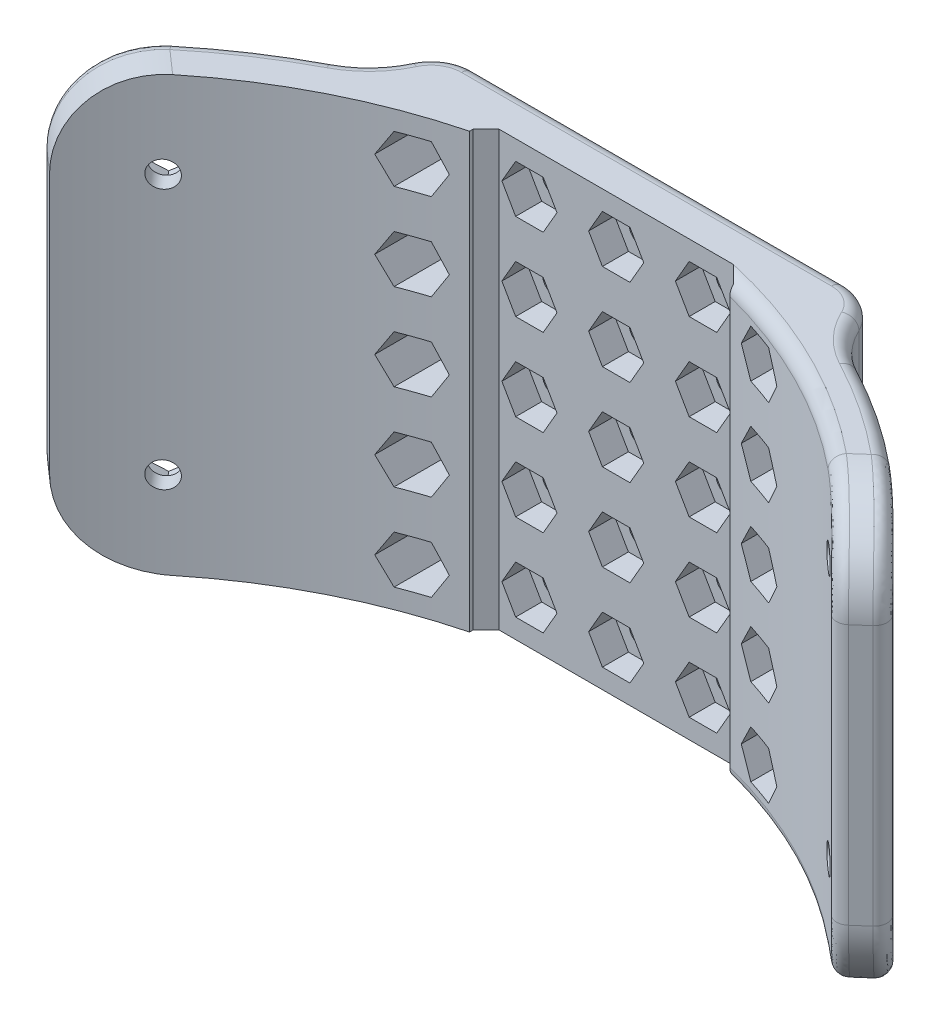
SolidWorks part; units mm, degrees
ref_plane "Front Plane" through (0, 0, 0) normal (0, 0, 1) x (1, 0, 0)
ref_plane "Top Plane" through (0, 0, 0) normal (0, 1, 0) x (1, 0, 0)
ref_plane "Right Plane" through (0, 0, 0) normal (1, 0, 0) x (0, 0, -1)
sketch "草图1" plane through (0, 0, 0) normal (0, 1, 0) x (1, 0, 0)
  line L1 (0, -1000) -> (0, 49000) construction
  line L2 (-15, 58.0948) -> (0, 0) construction
  line L3 (0, 0) -> (-45, 39.6863) construction
  line L6 (-48.75, 42.9935) -> (-45, 39.6863)
  line L7 (-15, 58.0948) -> (-15, 60)
  line L8 (-15, 60) -> (0, 60)
  line L9 (0, 60) -> (0, 65)
  line L11 (0, 65) -> (-25, 65)
  line L13 (-25, 65) -> (-25, 60)
  arc A0 (-45, 39.6863) -> (-15, 58.0948) centre (0, 0) cw
  arc A1 (-48.75, 42.9935) -> (-25, 60) centre (0, 0) cw
  arc A2 (-15, 58.0948) -> (0, 60) centre (0, 0) cw construction
  dimension "D1" = 60
  dimension "D2" = 45
  dimension "D3" = 5
  dimension "D4" = 25
  dimension "D5" = 5
  dimension "D6" = 15
extrude "凸台-拉伸1" add sketch "草图1" along normal blind 25 and the other way blind 25
mirror "镜向1" about plane through (0, 0, 0) normal (1, 0, 0) of "凸台-拉伸1"
sketch "草图2" plane through (0, 0, 0) normal (0, 1, 0) x (1, 0, 0)
  line L0 (0, 0) -> (-41.5552, 49.9816)
  line L1 (0, -1000) -> (0, 49000) construction
  line L2 (-48.75, 42.9935) -> (-45, 39.6863) construction
  arc A0 (-25, 60) -> (-48.75, 42.9935) centre (0, 0) ccw construction
  dimension "D1" = 10
ref_axis "基准轴1" through (0, -28.1623, 0) along (0, 1, 0)
ref_plane "基准面4" through (0, 0, 0) normal (-0.7689, 0, 0.6393) x (0.6393, 0, 0.7689)
ref_plane "基准面5" through (-41.5552, 0, -49.9816) normal (-0.6393, 0, -0.7689) x (0, 1, 0)
sketch "草图3" plane through (-41.5552, 0, -49.9816) normal (-0.6393, 0, -0.7689) x (0, 1, 0)
  line L0 (-15, 0) -> (15, 0) construction
  circle A0 centre (-15, 0) radius 1.5
  point P4 (0, 0)
  dimension "D2" = 3
  dimension "D1" = 30
extrude "切除-拉伸1" cut sketch "草图3" against normal through all
sketch "草图4" plane through (-41.5552, 0, -49.9816) normal (-0.6393, 0, -0.7689) x (0, 1, 0)
  line L1 (-11.8246, 0) -> (-13.4123, 2.75)
  line L2 (-13.4123, 2.75) -> (-16.5877, 2.75)
  line L3 (-16.5877, 2.75) -> (-18.1754, 0)
  line L4 (-18.1754, 0) -> (-16.5877, -2.75)
  line L5 (-16.5877, -2.75) -> (-13.4123, -2.75)
  line L6 (-13.4123, -2.75) -> (-11.8246, 0)
  circle A0 centre (-15, 0) radius 2.75 construction
  dimension "D1" = 5.5
extrude "切除-拉伸2" cut sketch "草图4" against normal blind 3
mirror "镜向2" about plane through (0, 0, 0) normal (0, 1, 0) of "切除-拉伸1", "切除-拉伸2"
mirror "镜向3" about plane through (0, 0, 0) normal (1, 0, 0) of "镜向2"
sketch "草图5" plane through (0, 0, -65) normal (0, 0, -1) x (-1, 0, 0)
  line L1 (-25, 25) -> (25, 25) construction
  line L2 (-25, -25) -> (-25, 25) construction
  circle A0 centre (-20, 20) radius 1.5
  dimension "D3" = 3
  dimension "D1" = 5
  dimension "D2" = 5
extrude "切除-拉伸3" cut sketch "草图5" against normal through all
ref_plane "基准面6" through (0, 0, -63) normal (0, 0, -1) x (-1, 0, 0)
sketch "草图6" plane through (0, 0, -63) normal (0, 0, -1) x (-1, 0, 0)
  line L1 (-16.8246, 20) -> (-18.4123, 22.75)
  line L2 (-18.4123, 22.75) -> (-21.5877, 22.75)
  line L3 (-21.5877, 22.75) -> (-23.1754, 20)
  line L4 (-23.1754, 20) -> (-21.5877, 17.25)
  line L5 (-21.5877, 17.25) -> (-18.4123, 17.25)
  line L6 (-18.4123, 17.25) -> (-16.8246, 20)
  circle A0 centre (-20, 20) radius 2.75 construction
  dimension "D1" = 5.5
extrude "切除-拉伸4" cut sketch "草图6" against normal through all
pattern_linear "阵列(线性)1" count 5 spacing 10 along (-1, 0, 0) count 5 spacing 10 along (0, -1, 0) of "切除-拉伸3", "切除-拉伸4"
fillet "圆角1" radius 10 4 edges at (-46.875, -25, -41.3399) (-46.875, 25, -41.3399) (46.875, -25, -41.3399) (46.875, 25, -41.3399)
fillet "圆角2" radius 10 2 edges at (-25, 0, -60) (25, 0, -60)
fillet "圆角3" radius 5 2 edges at (-25, 0, -65) (25, 0, -65)
fillet "圆角4" radius 1.5 2 edges at (-15, 0, -60) (15, 0, -60) profile chamfer
fillet "圆角5" radius 1.5 25 edges at (26.9937, -25, -53.5849) (42.4025, -22.839, -42.4503) (45, 0, -39.6863) (43.5213, 21.2455, -41.3024) (24.0095, -25, -64.2213) (27.6772, -25, -59.4712) (36.1006, -25, -54.0532) (47.2735, -21.2457, -44.6118) (48.75, 0, -42.9935) (46.1634, 22.8345, -45.7596) (36.1006, 25, -54.0532) (27.6772, 25, -59.4712) (24.0095, 25, -64.2213) (0, 25, -65) (-24.0095, 25, -64.2213) (-27.6772, 25, -59.4712) (-36.1006, 25, -54.0532) (-47.2735, 21.2457, -44.6118) (-48.75, 0, -42.9935) (-46.1634, -22.8345, -45.7596) (-36.1006, -25, -54.0532) (-27.6772, -25, -59.4712) (-24.0095, -25, -64.2213) (26.9937, 25, -53.5849) (0, -25, -65)
